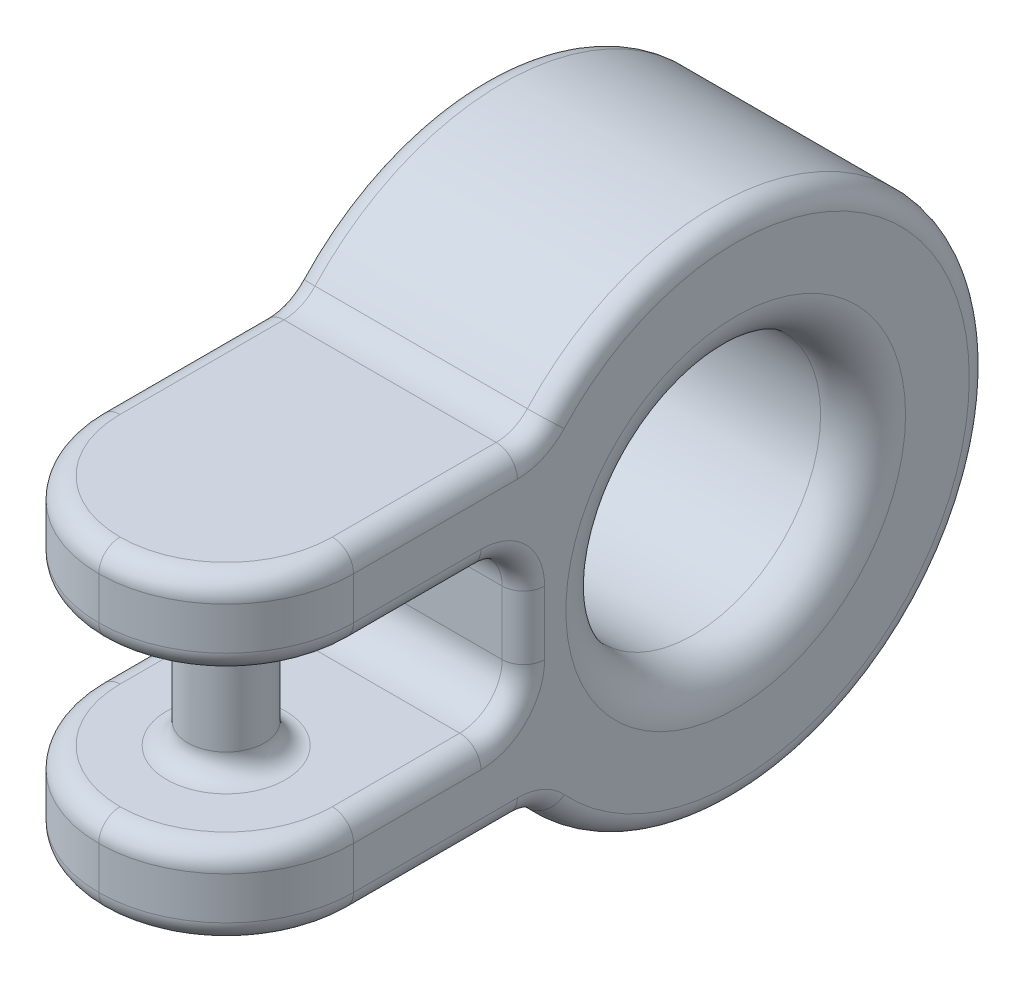
SolidWorks part; units mm, degrees
ref_plane "前视基准面" through (0, 0, 0) normal (0, 0, 1) x (1, 0, 0)
ref_plane "上视基准面" through (0, 0, 0) normal (0, 1, 0) x (1, 0, 0)
ref_plane "右视基准面" through (0, 0, 0) normal (1, 0, 0) x (0, 0, -1)
sketch "草图1" plane through (0, 0, 0) normal (1, 0, 0) x (0, 0, -1)
  line L0 (-4.6837, 3.75) -> (-12, 3.75)
  line L1 (-12, 3.75) -> (-12, 1.75)
  line L2 (-12, -3.75) -> (-4.6837, -3.75)
  line L3 (-12, 1.75) -> (-5, 1.75)
  line L4 (-12, -1.75) -> (-5, -1.75)
  line L5 (-5, 1.75) -> (-5, -1.75)
  line L6 (-12, -1.75) -> (-12, -3.75)
  circle A0 centre (0, 0) radius 3
  arc A1 (-4.6837, -3.75) -> (-4.6837, 3.75) centre (0, 0) ccw
  circle A2 centre (0, 0) radius 6 construction
  point P11 (-5, 0)
  dimension "D1" = 6
  dimension "D3" = 7
  dimension "D4" = 2
  dimension "D5" = 2
  dimension "D6" = 3.5
  dimension "D7" = 5
  dimension "D2" = 3
extrude "凸台-拉伸1" add sketch "草图1" along normal mid plane 6
fillet "圆角1" radius 1 4 edges at (0, 3.75, 4.6837) (0, -1.75, 5) (0, -3.75, 4.6837) (0, 1.75, 5)
sketch "草图2" plane through (0, -1.75, 0) normal (0, 1, 0) x (1, 0, 0)
  line L1 (3, -12) -> (-3, -12) construction
  circle A0 centre (0, -9) radius 0.9
  dimension "D1" = 1.8
  dimension "D2" = 3
extrude "凸台-拉伸2" add sketch "草图2" along normal up to next
fillet "圆角3" radius 1 2 edges at (-3, 0, -3) (3, 0, -3)
fillet "圆角2" radius 3 4 edges at (-3, -2.75, 12) (-3, 2.75, 12) (3, -2.75, 12) (3, 2.75, 12)
fillet "圆角4" radius 0.5 2 edges at (0, -1.75, 8.1) (0, 1.75, 9.9)
fillet "圆角5" radius 0.5 28 edges at (-2.1213, 3.75, 11.1213) (-3, 3.75, 7.0709) (-3, 3.8339, 4.7408) (-3, 0, -6) (-3, -3.8339, 4.7408) (-3, -3.75, 7.0709) (-2.1213, -3.75, 11.1213) (2.1213, -3.75, 11.1213) (3, -3.75, 7.0709) (3, -3.8339, 4.7408) (3, 0, -6) (3, 3.8339, 4.7408) (3, 3.75, 7.0709) (2.1213, 1.75, 11.1213) (-2.1213, 1.75, 11.1213) (-3, 1.75, 7.5) (-3, 1.4571, 5.2929) (-3, 0, 5) (-3, -1.4571, 5.2929) (-3, -1.75, 7.5) (-2.1213, -1.75, 11.1213) (2.1213, -1.75, 11.1213) (3, -1.75, 7.5) (3, -1.4571, 5.2929) (3, 0, 5) (3, 1.4571, 5.2929) (2.1213, 3.75, 11.1213) (3, 1.75, 7.5)
